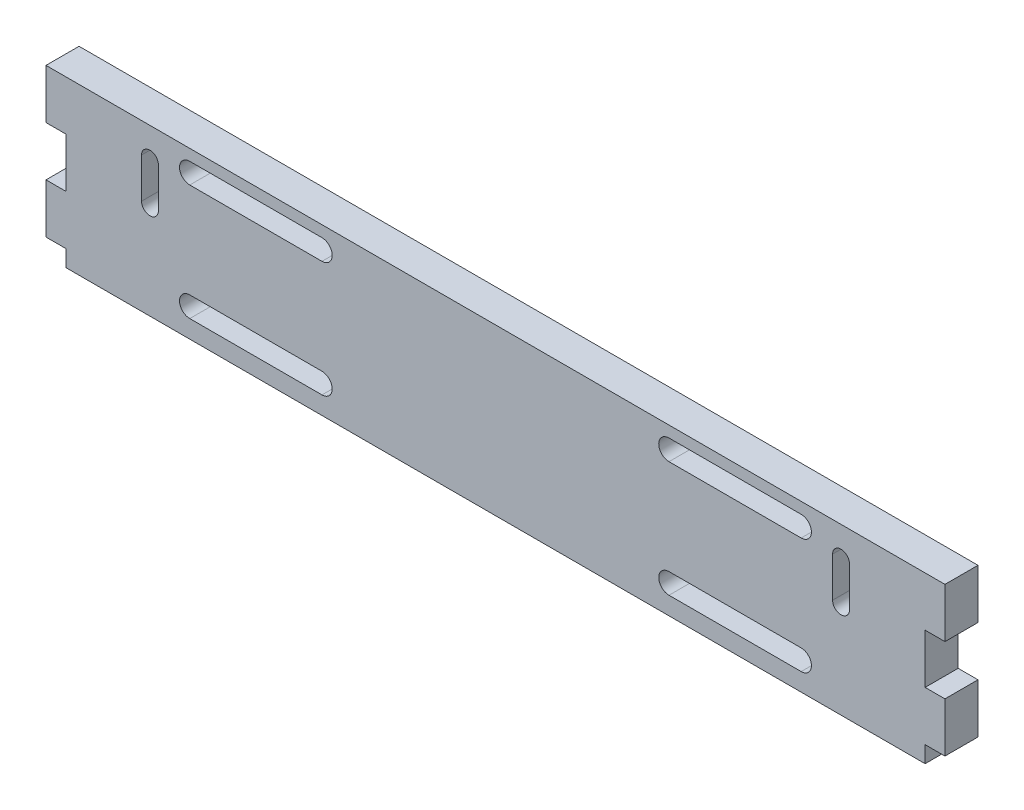
SolidWorks part; units mm, degrees
ref_plane "前基準面" through (0, 0, 0) normal (0, 0, 1) x (1, 0, 0)
ref_plane "上基準面" through (0, 0, 0) normal (0, 1, 0) x (1, 0, 0)
ref_plane "右基準面" through (0, 0, 0) normal (1, 0, 0) x (0, 0, -1)
sketch "草圖1" plane through (0, 0, 0) normal (0, 0, 1) x (1, 0, 0)
  line L0 (136, -22.5) -> (136, -7.5)
  line L1 (136, 22.5) -> (-136, 22.5)
  line L2 (130, 7.5) -> (130, -7.5)
  line L3 (130, -27.5) -> (-130, -27.5)
  line L4 (-130, 7.5) -> (-130, -7.5)
  line L5 (0, -27.5) -> (0, 22.5) construction
  line L6 (130, 0) -> (-130, 0) construction
  line L9 (-130, 7.5) -> (-136, 7.5)
  line L10 (-136, 22.5) -> (-136, 7.5)
  line L14 (-136, -22.5) -> (-136, -7.5)
  line L15 (130, -7.5) -> (136, -7.5)
  line L16 (130, 7.5) -> (136, 7.5)
  line L17 (136, 22.5) -> (136, 7.5)
  line L18 (-136, -22.5) -> (-130, -22.5)
  line L19 (-130, -22.5) -> (-130, -27.5)
  line L20 (-136, -7.5) -> (-130, -7.5)
  line L21 (130, -22.5) -> (130, -27.5)
  line L22 (130, -22.5) -> (136, -22.5)
  point P0 (0, 0)
  point P8 (0, 0)
  point P13 (-136, -15)
  point P14 (136, -15)
  dimension "D1" = 260
  dimension "D2" = 6
  dimension "D3" = 15
  dimension "D4" = 6
  dimension "D5" = 50
  dimension "D6" = 5
extrude "填料-伸長1" add sketch "草圖1" along normal blind 10
sketch "草圖2" plane through (0, 0, 10) normal (0, 0, 1) x (1, 0, 0)
  line L0 (-92.5, 16) -> (-52.5, 16) construction
  line L1 (-92.5, 19.1) -> (-52.5, 19.1)
  line L2 (-92.5, 12.9) -> (-52.5, 12.9)
  line L3 (-92.5, -19) -> (-52.5, -19) construction
  line L4 (-92.5, -15.9) -> (-52.5, -15.9)
  line L5 (-92.5, -22.1) -> (-52.5, -22.1)
  line L6 (0, 61.8937) -> (0, -44.053) construction
  line L7 (-130, -27.5) -> (130, -27.5) construction
  line L8 (52.5, 16) -> (92.5, 16) construction
  line L9 (52.5, 19.1) -> (92.5, 19.1)
  line L10 (52.5, 12.9) -> (92.5, 12.9)
  line L11 (52.5, -19) -> (92.5, -19) construction
  line L12 (52.5, -15.9) -> (92.5, -15.9)
  line L13 (52.5, -22.1) -> (92.5, -22.1)
  arc A0 (-92.5, 19.1) -> (-92.5, 12.9) centre (-92.5, 16) ccw
  arc A1 (-52.5, 12.9) -> (-52.5, 19.1) centre (-52.5, 16) ccw
  arc A2 (-92.5, -15.9) -> (-92.5, -22.1) centre (-92.5, -19) ccw
  arc A3 (-52.5, -22.1) -> (-52.5, -15.9) centre (-52.5, -19) ccw
  arc A4 (52.5, 19.1) -> (52.5, 12.9) centre (52.5, 16) ccw
  arc A5 (92.5, 12.9) -> (92.5, 19.1) centre (92.5, 16) ccw
  arc A6 (52.5, -15.9) -> (52.5, -22.1) centre (52.5, -19) ccw
  arc A7 (92.5, -22.1) -> (92.5, -15.9) centre (92.5, -19) ccw
  point P2 (-72.5, 16)
  point P7 (-72.5, -19)
  point P22 (72.5, 16)
  point P27 (72.5, -19)
  point P37 (-95.6, -19)
  point P38 (49.4, -19)
  dimension "D3" = 3.1
  dimension "D1" = 35
  dimension "D2" = 5.4
  dimension "D4" = 40
  dimension "D6" = 145
  dimension "D5" = 2
extrude "除料-伸長1" cut sketch "草圖2" against normal through all
sketch "草圖5" plane through (0, 0, 10) normal (0, 0, 1) x (1, 0, 0)
  line L0 (-130, -27.5) -> (130, -27.5) construction
  line L1 (-46.5, -27.5) -> (-98.5, -27.5) construction
  line L2 (-46.5, -27.5) -> (-46.5, 24.5) construction
  line L3 (-46.5, 24.5) -> (-98.5, 24.5) construction
  line L4 (-98.5, -27.5) -> (-98.5, 24.5) construction
  line L5 (-136, 22.5) -> (-136, 7.5) construction
  line L6 (-112.3, 7.4) -> (-99.5, 7.4) construction
  line L7 (-112.3, 20) -> (-99.5, 20) construction
  line L8 (-112.3, 20) -> (-112.3, -5.2) construction
  line L9 (-112.3, -5.2) -> (-99.5, -5.2) construction
  line L10 (-99.5, 20) -> (-99.5, -5.2) construction
  line L11 (-107.1, 13.45) -> (-107.1, 1.35)
  line L12 (-102, 1.35) -> (-102, 13.45)
  line L13 (0, 31.8405) -> (0, -38.3898) construction
  line L14 (107.1, 13.45) -> (107.1, 1.35)
  line L15 (102, 1.35) -> (102, 13.45)
  arc A0 (-102, 13.45) -> (-107.1, 13.45) centre (-104.55, 13.45) ccw
  arc A1 (-107.1, 1.35) -> (-102, 1.35) centre (-104.55, 1.35) ccw
  arc A2 (102, 13.45) -> (107.1, 13.45) centre (104.55, 13.45) cw
  arc A3 (107.1, 1.35) -> (102, 1.35) centre (104.55, 1.35) cw
  point P16 (-104.55, 3.9)
  point P17 (-104.55, 10.9)
  point P20 (-104.55, 16)
  point P22 (-107.1, 13.45)
  point P25 (-102, 13.45)
  dimension "D5" = 7
  dimension "D6" = 5.1
  dimension "D1" = 52
  dimension "D2" = 37.5
  dimension "D3" = 52
  dimension "D4" = 12.8
  dimension "D7" = 2.5
  dimension "D8" = 47.5
  dimension "D9" = 4
  dimension "D10" = 1
  dimension "D11" = 12.1
extrude "除料-伸長2" cut sketch "草圖5" against normal through all
